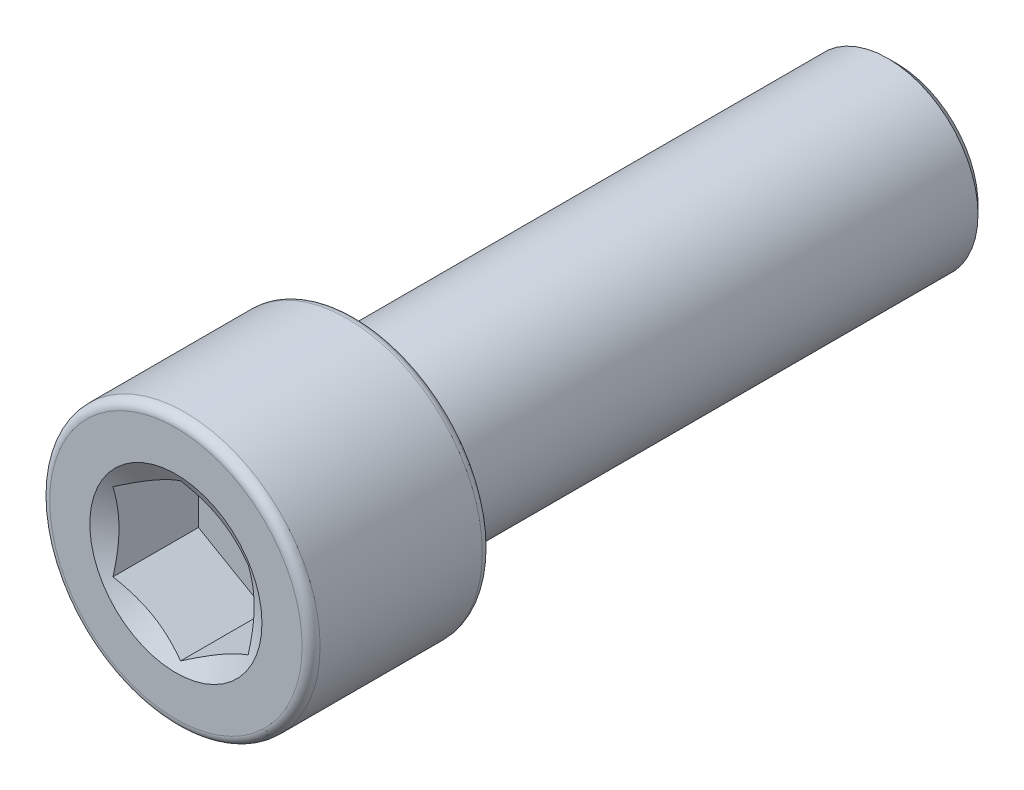
SolidWorks part; units mm, degrees
material "Alloy Steel"
ref_plane "Front Plane" through (0, 0, 0) normal (0, 0, 1) x (1, 0, 0)
ref_plane "Top Plane" through (0, 0, 0) normal (0, 1, 0) x (1, 0, 0)
ref_plane "Right Plane" through (0, 0, 0) normal (1, 0, 0) x (0, 0, -1)
sketch "Sketch1" plane through (0, 0, 0) normal (1, 0, 0) x (0, 0, -1)
  line L0 (12.7, 0) -> (-12.7, 0) construction
  line L1 (-6.35, 4.7625) -> (-6.35, -4.7625) construction
  line L2 (12.7, 3.175) -> (12.7, -3.175) construction
  line L3 (12.6206, 3.3125) -> (13.2556, 2.2126) construction
  line L4 (13.1763, 2.3501) -> (13.335, 2.3501) construction
  line L5 (13.2556, 2.2126) -> (13.8906, 3.3125) construction
  line L6 (13.8906, 3.3125) -> (12.6206, 3.3125) construction
  line L7 (13.2556, 2.3501) -> (13.2556, 2.2126) construction
  line L8 (13.2556, 3.3125) -> (13.2556, 3.175) construction
  line L9 (13.8113, 3.175) -> (12.7, 3.175) construction
  point P4 (-6.35, 0)
  point P6 (-6.35, 2.3812)
  point P7 (8.255, -3.175)
  point P20 (13.2556, 3.2437)
  dimension "Head Height" = 6.35
  dimension "Head Diameter" = 9.525
  dimension "Drive Size" = 4.7625
  dimension "Length" = 19.05
  dimension "Screw Size Decimal Equivalent" = 6.35
  dimension "Pitch" = 1.27
  dimension "Pitch/8" = 0.1588
  dimension "Thread Note" = 4.445
sketch "Sketch2" plane through (0, 0, 0) normal (1, 0, 0) x (0, 0, -1)
  line L0 (12.7, 0) -> (12.7, 2.8575)
  line L1 (12.7, 3.175) -> (12.7, -3.175) construction
  line L2 (12.7, 2.8575) -> (12.3825, 3.175)
  line L3 (12.3825, 3.175) -> (-6.35, 3.175)
  line L4 (-6.35, 3.175) -> (-6.35, 4.445)
  line L5 (-6.6675, 4.7625) -> (-12.3825, 4.7625)
  line L6 (-12.7, 4.445) -> (-12.7, 0)
  line L7 (12.7, 0) -> (-12.7, 0) construction
  line L8 (-12.7, 0) -> (12.7, 0)
  arc A0 (-6.35, 4.445) -> (-6.6675, 4.7625) centre (-6.6675, 4.445) ccw
  arc A1 (-12.3825, 4.7625) -> (-12.7, 4.445) centre (-12.3825, 4.445) ccw
  point P19 (-6.35, 4.7625)
  dimension "D3" = 0.3175
  dimension "D1" = 0.3175
  dimension "D2" = 45
revolve "Revolve1" add sketch "Sketch2" angle 360 about L0
sketch "Sketch3" plane through (0, 0, 0) normal (0, 0, 1) x (1, 0, 0)
  line L1 (-2.3812, 1.3748) -> (-2.3812, -1.3748)
  line L2 (-2.3812, -1.3748) -> (0, -2.7496)
  line L3 (0, -2.7496) -> (2.3812, -1.3748)
  line L4 (2.3812, -1.3748) -> (2.3812, 1.3748)
  line L5 (2.3812, 1.3748) -> (0, 2.7496)
  line L6 (0, 2.7496) -> (-2.3812, 1.3748)
  circle A0 centre (0, 0) radius 2.3812 construction
  circle A1 centre (0, 0) radius 4.7625 construction
extrude "Cut-Extrude1" cut sketch "Sketch3" against normal blind 3.175 from vertex starting at point (0, 0, 12.7)
sketch "Sketch4" plane through (0, 0, 12.7) normal (0, 0, 1) x (1, 0, 0)
  line L0 (0, 2.7496) -> (0, 3.3148) construction
  line L1 (0, 3.3148) -> (0, 3.8799) construction
  line L2 (0, 3.8799) -> (0, 4.445) construction
  circle A0 centre (0, 0) radius 3.0322
  point P12 (0, 3.0322)
extrude "Cut-Extrude2" cut sketch "Sketch4" against normal through all draft 60
split "Split1" [suppressed] bodies to split 106 112
sketch "Sketch5" [suppressed] plane through (0, 0, 0) normal (1, 0, 0) x (0, 0, -1)
  line L0 (13.1763, 2.3501) -> (13.335, 2.3501)
  line L1 (13.335, 2.3501) -> (13.8509, 3.2437)
  line L2 (13.8509, 3.2437) -> (12.6603, 3.2437)
  line L3 (12.6603, 3.2437) -> (13.1763, 2.3501)
  line L4 (12.6206, 3.3125) -> (13.2556, 2.2126) construction
sketch "Sketch6" [suppressed] plane through (0, 0, -12.7) normal (0, 0, -1) x (-1, 0, 0)
  circle A0 centre (0, 0) radius 3.175
curve "Helix/Spiral1" [suppressed] pitch 1.27 height 20.32 turns 16
sweep "Cut-Sweep1" [suppressed] cut profiles "Sketch5" path "Helix/Spiral1"
sketch "Sketch7" [suppressed] plane through (0, 0, 6.35) normal (0, 0, -1) x (-1, 0, 0)
  circle A0 centre (0, 0) radius 3.2258
  circle A1 centre (0, 0) radius 3.175 construction
  dimension "D1" = 0.0508
extrude "Boss-Extrude1" [suppressed] add sketch "Sketch7" along normal through all draft 20 and the other way blind 0.635
ref_plane "Plane1" [suppressed] through (0, 0, 8.4455) normal (0, 0, -1) x (-1, 0, 0)
sketch "Sketch13" [suppressed] plane through (0, 0, 8.4455) normal (0, 0, -1) x (-1, 0, 0)
  line L0 (0.1191, 4.761) -> (0, 0) construction
  line L1 (0, 0) -> (-0.1191, 4.761) construction
  line L3 (0.1171, 4.6824) -> (0.1191, 4.761)
  line L6 (-0.1171, 4.6824) -> (-0.1191, 4.761)
  arc A1 (0.1191, 4.761) -> (-0.1191, 4.761) centre (0, 0) ccw
  circle A2 centre (0, 0) radius 4.7625 construction
  arc A3 (0.1171, 4.6824) -> (-0.1171, 4.6824) centre (0, 0) ccw
  point P2 (0, 4.7625)
  dimension "D3" = 0.0786
  dimension "D1" = 0.2381
extrude "Cut-Extrude3" [suppressed] cut sketch "Sketch13" against normal blind 3.5433
chamfer "Chamfer3" [suppressed] distance 0.0786 angle 60
chamfer "Chamfer4" [suppressed] distance 0.0786 angle 85
pattern_circular "CirPattern2" [suppressed] count 50 over 360 about axis through (0, 0, -12.7) along (0, 0, 1) of bodies 134
equation "\"Pitch/8@Sketch1\" = \"Pitch@Sketch1\" / 8"
equation "\"Thread Note@Sketch1\" = \"Pitch@Sketch1\" * 3.5"
equation "\"D1@Sketch2\"=\"Pitch@Sketch1\"*.25"
equation "\"D3@Sketch2\"=\"Head Height@Sketch1\"*.05"
equation "\"D1@Cut-Extrude1\" = \"Head Height@Sketch1\" * .5"
equation "\"D3@Helix/Spiral1\" = \"Length@Sketch1\" + \"Pitch@Sketch1\""
equation "\"D4@Helix/Spiral1\" = \"Pitch@Sketch1\""
equation "\"D2@Boss-Extrude1\" = \"Head Height@Sketch1\" * .1"
equation "\"D1\"= \"Screw Size Decimal Equivalent@Sketch1\" * .4"
equation "\"D1@Plane1\"=\"Head Height@Sketch1\" * .33"
equation "\"D1@Cut-Extrude3\"=( \"Head Height@Sketch1\" - \"D1@Plane1\" - \"D3@Sketch2\" )  * .9"
equation "\"D1@Chamfer3\"=\"D3@Sketch13\""
equation "\"D1@Chamfer4\"=\"D3@Sketch13\""
equation "\"D1@CirPattern2\"=( \"Head Diameter@Sketch1\" * pi )  /  ( 2.5*\"D1@Sketch13\" )"
equation "\"D1@Sketch13\"=\"Head Diameter@Sketch1\" * .025"
equation "\"D3@Sketch13\"=\"D1@Sketch13\"*.33"
